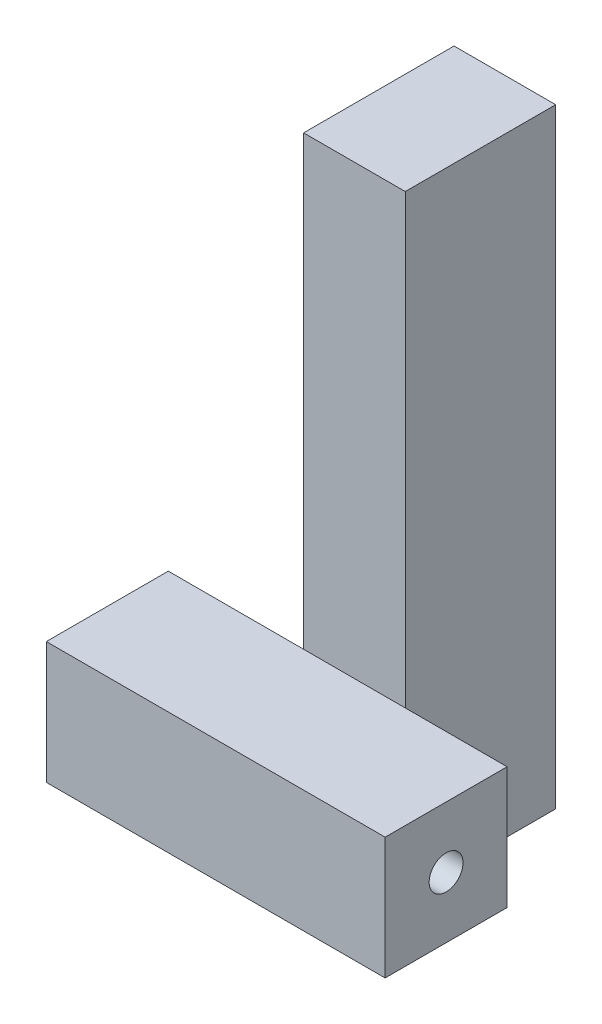
SolidWorks part; units mm, degrees
ref_plane "Front Plane" through (0, 0, 0) normal (0, 0, 1) x (1, 0, 0)
ref_plane "Top Plane" through (0, 0, 0) normal (0, 1, 0) x (1, 0, 0)
ref_plane "Right Plane" through (0, 0, 0) normal (1, 0, 0) x (0, 0, -1)
sketch "Sketch1" plane through (0, 0, 0) normal (0, 0, 1) x (1, 0, 0)
  line L1 (-63.5, 22.86) -> (63.5, 22.86)
  line L2 (-63.5, 22.86) -> (-63.5, -22.86)
  line L3 (-63.5, -22.86) -> (63.5, -22.86)
  line L4 (63.5, 22.86) -> (63.5, -22.86)
  line L5 (-63.5, 22.86) -> (63.5, -22.86) construction
  line L6 (-63.5, -22.86) -> (63.5, 22.86) construction
  point P0 (0, 0)
  dimension "D1" = 45.72
  dimension "D2" = 127
extrude "Boss-Extrude1" add sketch "Sketch1" along normal blind 45.72
sketch "Sketch2" plane through (0, 0, 0) normal (0, 0, -1) x (-1, 0, 0)
  line L0 (63.5, -22.86) -> (-63.5, -22.86) construction
  line L1 (12.7738, -38.1) -> (-25.3262, -38.1)
  line L2 (12.7738, -38.1) -> (12.7738, 190.5)
  line L3 (12.7738, 190.5) -> (-25.3262, 190.5)
  line L4 (-25.3262, -38.1) -> (-25.3262, 190.5)
  dimension "D1" = 15.24
  dimension "D2" = 38.1
  dimension "D3" = 228.6
extrude "Boss-Extrude2" add sketch "Sketch2" along normal blind 56.388
sketch "Sketch3" plane through (63.5, 0, 0) normal (1, 0, 0) x (0, 0, -1)
  line L0 (-22.86, 22.86) -> (-22.86, 0) construction
  line L1 (-45.72, 22.86) -> (0, 22.86) construction
  line L2 (0, 0) -> (-22.86, 0) construction
  circle A0 centre (-22.86, 0) radius 6.35
  dimension "D1" = 12.7
extrude "Cut-Extrude1" cut sketch "Sketch3" against normal blind 12.7
sketch "Sketch4" plane through (-63.5, 0, 0) normal (-1, 0, 0) x (0, 0, 1)
  line L0 (22.86, 22.86) -> (22.86, 0) construction
  line L1 (45.72, 22.86) -> (0, 22.86) construction
  line L2 (0, 0) -> (22.86, 0) construction
  line L3 (0, 22.86) -> (0, -22.86) construction
  circle A0 centre (22.86, 0) radius 6.35
  dimension "D1" = 12.7
extrude "Cut-Extrude2" cut sketch "Sketch4" against normal blind 12.7
